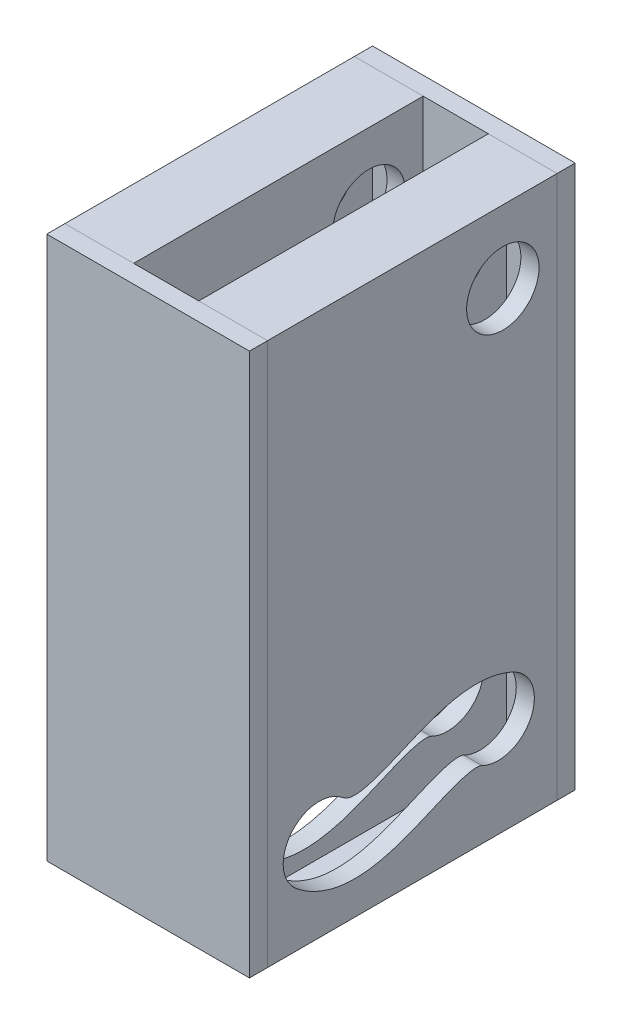
SolidWorks part; units mm, degrees
ref_plane "Front Plane" through (0, 0, 0) normal (0, 0, 1) x (1, 0, 0)
ref_plane "Top Plane" through (0, 0, 0) normal (0, 1, 0) x (1, 0, 0)
ref_plane "Right Plane" through (0, 0, 0) normal (1, 0, 0) x (0, 0, -1)
sketch "Sketch1" plane through (0, 0, 0) normal (0, 0, 1) x (1, 0, 0)
  line L0 (-9, 75) -> (-9, 35)
  line L8 (-9, -35) -> (-9, -75)
  line L9 (-9, -75) -> (-28, -75)
  line L10 (-28, -75) -> (-28, 75)
  line L11 (-28, 75) -> (-9, 75)
  line L12 (0, 171.0434) -> (0, -171.0434) construction
  line L13 (-9, 35) -> (9, 35)
  line L14 (-9, -35) -> (9, -35)
  line L15 (9, -35) -> (9, -75)
  line L16 (9, -75) -> (28, -75)
  line L17 (28, -75) -> (28, 75)
  line L18 (9, 75) -> (9, 35)
  line L19 (28, 75) -> (9, 75)
  line L20 (-23, 70) -> (-14, 70)
  line L21 (-14, 70) -> (-14, 30)
  line L22 (-14, 30) -> (14, 30)
  line L23 (14, 70) -> (14, 30)
  line L24 (23, 70) -> (14, 70)
  line L25 (23, -70) -> (23, 70)
  line L26 (14, -70) -> (23, -70)
  line L27 (14, -30) -> (14, -70)
  line L28 (-14, -30) -> (14, -30)
  line L29 (-14, -30) -> (-14, -70)
  line L30 (-14, -70) -> (-23, -70)
  line L31 (-23, -70) -> (-23, 70)
  line L32 (-66.2515, 55) -> (66.2515, 55) construction
  line L33 (-23, 0) -> (23, 0) construction
  line L34 (-28, 65) -> (28, 65) construction
  line L35 (-28, -65) -> (28, -65) construction
  line L36 (-66.2515, -55) -> (66.2515, -55) construction
  point P6 (0, -35)
  point P16 (0, 35)
  point P31 (0, 0)
  point P34 (0, 55)
  point P35 (-9, 55)
  dimension "D2" = 10
  dimension "D3" = 18
  dimension "D4" = 56
  dimension "D5" = 150
  dimension "D6" = 20
  dimension "D1" = 5
sketch "Sketch2" plane through (0, 0, 0) normal (1, 0, 0) x (0, 0, -1)
  line L0 (-30, 0) -> (50, 0) construction
  line L1 (-30, 0) -> (-35, 0) construction
  line L2 (50, 0) -> (55, 0) construction
  dimension "D1" = 80
  dimension "D2" = 5
  dimension "D3" = 50
extrude "Boss-Extrude1" add sketch "Sketch1" along normal up to vertex (30 mm away) and the other way up to vertex (50 mm away) up to point (0, 0, 30) other way up to point (0, 0, -50)
sketch "Sketch3" plane through (0, 0, 0) normal (0, 0, 1) x (1, 0, 0)
  line L1 (-28, -75) -> (28, -75)
  line L2 (-28, -75) -> (-28, 75)
  line L3 (-28, 75) -> (28, 75)
  line L4 (28, -75) -> (28, 75)
  line L5 (-28, -75) -> (28, 75) construction
  line L6 (-28, 75) -> (28, -75) construction
  point P0 (0, 0)
extrude "Boss-Extrude2" add sketch "Sketch3" along normal up to vertex (35 mm away) from vertex separate body up to point (0, 0, 35) starting at point (0, 0, 30)
extrude "Boss-Extrude3" add sketch "Sketch3<2>" against normal up to vertex (55 mm away) from vertex separate body up to point (0, 0, -55) starting at point (0, 0, -50)
sketch "Sketch3<2>" plane through (0, 0, 0) normal (0, 0, 1) x (1, 0, 0) same geometry as "Sketch3"
sketch "Sketch4" plane through (0, 0, 0) normal (1, 0, 0) x (0, 0, -1)
  line L0 (0, 171.0434) -> (0, -171.0434) construction
  line L1 (0, 0) -> (0, 55) construction
  line L2 (0, 55) -> (35, 55) construction
  line L3 (-11.8844, -55.7997) -> (0.1156, -55.7997) construction
  line L5 (-10.8844, -60.7997) -> (-0.8844, -60.7997) construction
  line L6 (-10.8844, -60.7997) -> (-10.8844, -50.7997) construction
  line L7 (-10.8844, -50.7997) -> (-0.8844, -50.7997) construction
  line L8 (-0.8844, -60.7997) -> (-0.8844, -50.7997) construction
  line L9 (-10.8844, -60.7997) -> (-0.8844, -50.7997) construction
  line L10 (-10.8844, -50.7997) -> (-0.8844, -60.7997) construction
  arc A2 (-21.9612, -60.1535) -> (-9.4142, -44.5787) centre (-15.6877, -52.3661) cw
  arc A3 (29.2096, -56.2677) -> (38.2188, -38.4118) centre (33.7142, -47.3397) ccw
  circle A4 centre (35, 55) radius 10
  spline S0 degree 3 poles (-15.6877, -52.3661) (-0.6676, -64.4663) (19.4244, -40.1299) (33.7142, -47.3397) knots 0 0 0 0 1 1 1 1 construction
  spline S1 degree 1 poles (-21.9612, -60.1535) (29.2096, -56.2677) knots 0 0 1 1 construction
  spline S2 degree 3 poles (-21.9612, -60.1535) (-21.2326, -60.7404) (-19.7049, -61.8467) (-16.5047, -63.6733) (-12.2723, -65.2199) (-7.2245, -65.9156) (-0.896, -65.6402) (6.0756, -63.823) (13.3281, -60.8744) (19.6872, -58.0691) (24.0439, -56.5285) (26.6043, -56.0154) (27.9543, -55.9488) (28.7219, -56.0631) (29.04, -56.1821) (29.2096, -56.2677) knots 0 0 0 0 0.03125 0.0625 0.125 0.1875 0.25 0.375 0.5 0.625 0.75 0.8125 0.875 0.9375 1 1 1 1
  spline S3 degree 1 poles (-9.4142, -44.5787) (38.2188, -38.4118) knots 0 0 1 1 construction
  spline S4 degree 3 poles (-9.4142, -44.5787) (-9.3177, -44.6565) (-9.113, -44.8128) (-8.7501, -45.0598) (-8.3333, -45.2957) (-7.8736, -45.4934) (-7.2533, -45.6849) (-6.3508, -45.8249) (-4.8225, -45.7841) (-2.8135, -45.4329) (0.4161, -44.5109) (5.2569, -42.5771) (11.8945, -39.6457) (18.0981, -37.3535) (23.6968, -36.1642) (28.2903, -35.8349) (32.4283, -36.3113) (35.7677, -37.2971) (37.4231, -38.0103) (38.2188, -38.4118) knots 0 0 0 0 0.015625 0.03125 0.0625 0.09375 0.125 0.1875 0.25 0.3125 0.375 0.5 0.625 0.75 0.8125 0.875 0.9375 0.96875 1 1 1 1
  point P6 (-11.4673, -61.0039)
  point P10 (0, -55)
  point P21 (0, 0)
  point P22 (0, -55)
  point P28 (-4.2175, -54.5652)
  point P29 (-4.3161, -60.601)
  point P30 (-4.9879, -58.816)
  point P31 (-5.8844, -55.7997)
  point P32 (-3.3336, -58.2914)
  point P33 (6.4528, -51.1591)
  point P34 (5.1304, -60.4965)
  point P35 (8.4328, -51.4065)
  point P36 (9.8137, -56.9211)
  point P37 (-11.4729, -61.0057)
  dimension "D1" = 10
  dimension "D2" = 10
  dimension "D4" = 35
  dimension "D5" = 20
  dimension "D6" = 12
  dimension "D3" = 10
extrude "Cut-Extrude1" cut sketch "Sketch4" against normal through all and the other way through all contours A4 | S4 A2 S2 A3 L8 L5 L6 L7 | L5 L8 L7 L6 region at (0, -50.8563, -8.874) region at (0, 55, -35)
